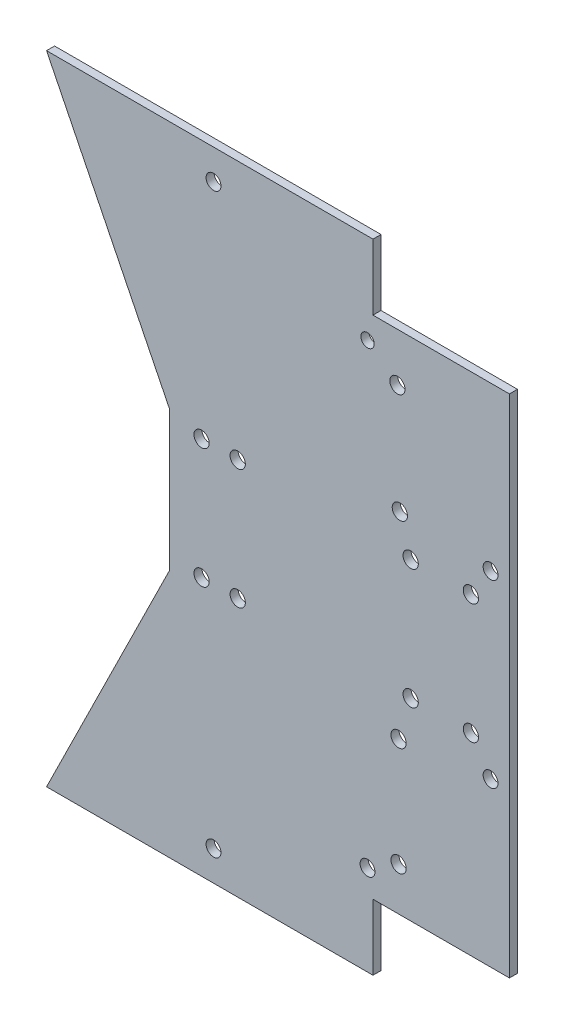
SolidWorks part; units mm, degrees
material "Thornel Mat VMA"
ref_plane "Front Plane" through (0, 0, 0) normal (0, 0, 1) x (1, 0, 0)
ref_plane "Top Plane" through (0, 0, 0) normal (0, 1, 0) x (1, 0, 0)
ref_plane "Right Plane" through (0, 0, 0) normal (1, 0, 0) x (0, 0, -1)
sketch "Sketch2" plane through (0, 0, 0) normal (0, 0, 1) x (-1, 0, 0)
  line L11 (-2.9301, 168.7083) -> (38.7094, 168.7083)
  line L12 (-2.9301, 8.6883) -> (38.7094, 8.6883)
  line L13 (38.7094, -12.1397) -> (38.7094, 8.6883)
  line L14 (143.4971, -12.1397) -> (38.7094, -12.1397)
  line L15 (38.7094, 189.5363) -> (38.7094, 168.7083)
  line L16 (143.4971, 189.5363) -> (38.7094, 189.5363)
  line L17 (104.6174, 110.8598) -> (143.4971, 189.5363)
  line L18 (104.6174, 66.5368) -> (143.4971, -12.1397)
  line L19 (104.6174, 66.5368) -> (72.8674, 66.5368)
  line L20 (72.8674, 66.5368) -> (72.8674, 110.8598)
  line L21 (104.6174, 110.8598) -> (72.8674, 110.8598)
  line L22 (-2.9301, 168.7083) -> (-2.9301, 8.6883)
  line L23 (41.9566, 19.6103) -> (41.9566, 13.2603) construction
  circle A0 centre (41.9566, 160.9613) radius 2.3495
  circle A1 centre (90.6739, 180.0113) radius 2.3495
  circle A2 centre (90.6739, -2.6147) radius 2.3495
  circle A3 centre (3.0351, 117.2098) radius 2.3495
  circle A4 centre (3.0351, 60.1868) radius 2.3495
  circle A5 centre (41.9566, 16.4353) radius 2.0955
  point P36 (41.9566, 16.4353)
  dimension "D3" = 4.699
  dimension "D7" = 31.75
  dimension "D8" = 41.6395
  dimension "D9" = 20.828
  dimension "D10" = 160.02
  dimension "D11" = 20.828
  dimension "D12" = 41.6395
  dimension "D13" = 104.7876
  dimension "D14" = 116.297
  dimension "D15" = 116.297
  dimension "D16" = 44.323
  dimension "D17" = 26.297
  dimension "D18" = 9.525
  dimension "D19" = 28.575
  dimension "D20" = 7.747
  dimension "D21" = 51.9645
  dimension "D22" = 51.4985
  dimension "D23" = 5.9651
  dimension "D24" = 51.4985
  dimension "D25" = 5.9651
  dimension "D26" = 7.747
  dimension "D27" = 3.2471
  dimension "D28" = 9.525
  dimension "D29" = 51.9645
extrude "Boss-Extrude1" add sketch "Sketch2" along normal blind 2.54
sketch "Sketch3" plane through (0, 0, 2.54) normal (0, 0, 1) x (1, 0, 0)
  line L1 (-104.6174, -66.5368) -> (-72.8674, -66.5368)
  line L2 (-104.6174, -66.5368) -> (-104.6174, -110.8598)
  line L3 (-104.6174, -110.8598) -> (-72.8674, -110.8598)
  line L4 (-72.8674, -66.5368) -> (-72.8674, -110.8598)
extrude "Boss-Extrude2" add sketch "Sketch3" against normal up to surface (2.54 mm away) up to face at (-65.9118, -88.6983, 0)
sketch "Sketch4" plane through (0, 0, 2.54) normal (0, 0, 1) x (1, 0, 0)
  line L0 (-104.6174, -66.5368) -> (-104.6174, -72.8868)
  line L1 (-104.6174, -66.5368) -> (-104.6174, -110.8598) construction
  line L2 (-104.6174, -69.7118) -> (2.9301, -69.7118) construction
  line L3 (2.9301, -168.7083) -> (2.9301, -8.6883) construction
  line L4 (-104.6174, -88.6983) -> (2.9301, -88.6983) construction
  line L5 (-104.6174, -107.6848) -> (2.9301, -107.6848) construction
  line L6 (-104.6174, -110.8598) -> (-104.6174, -104.5098)
  circle A0 centre (-94.4574, -69.7118) radius 2.413
  circle A1 centre (-83.0274, -69.7118) radius 2.413
  circle A2 centre (-28.3119, -69.7118) radius 2.413
  circle A3 centre (-9.2619, -69.7118) radius 2.413
  circle A4 centre (-9.2619, -107.6848) radius 2.413
  circle A5 centre (-28.3119, -107.6848) radius 2.413
  circle A6 centre (-83.0274, -107.6848) radius 2.413
  circle A7 centre (-94.4574, -107.6848) radius 2.413
  dimension "D2" = 10.16
  dimension "D4" = 4.826
  dimension "D5" = 4.826
  dimension "D8" = 4.826
  dimension "D9" = 4.826
  dimension "D1" = 3.175
  dimension "D3" = 11.43
  dimension "D6" = 19.05
  dimension "D7" = 12.192
extrude "Cut-Extrude1" cut sketch "Sketch4" against normal through all contours A0 | A1 | A2 | A3 | A4 | A5 | A6 | A7
sketch "Sketch5" plane through (0, 0, 2.54) normal (0, 0, 1) x (1, 0, 0)
  circle A0 centre (-31.739, -58.2731) radius 2.413
  dimension "D1" = 4.826
sketch "Sketch6" plane through (0, 0, 2.54) normal (0, 0, 1) x (1, 0, 0)
  circle A0 centre (-32.5114, -23.9918) radius 2.413
  dimension "D1" = 4.826
extrude "Cut-Extrude2" cut sketch "Sketch5" against normal through all
extrude "Cut-Extrude3" cut sketch "Sketch6" against normal through all
sketch "Sketch7" plane through (0, 0, 2.54) normal (0, 0, 1) x (1, 0, 0)
  circle A0 centre (-32.1405, -155.0714) radius 2.413
  circle A1 centre (-32.1405, -120.7814) radius 2.413
  dimension "D1" = 4.826
  dimension "D2" = 4.826
extrude "Cut-Extrude4" cut sketch "Sketch7" against normal through all
sketch "Sketch8" plane through (0, 0, 2.54) normal (0, 0, 1) x (1, 0, 0)
  line L0 (-38.7094, -168.7083) -> (2.9301, -168.7083) construction
  line L1 (-32.2387, 12.4252) -> (-40.2334, 12.4252)
  line L2 (-32.2387, 12.4252) -> (-32.2387, -8.6883)
  line L3 (-32.2387, -8.6883) -> (-40.2334, -8.6883)
  line L4 (-40.2334, 12.4252) -> (-40.2334, -8.6883)
  line L5 (-18.7398, -197.6692) -> (-40.2334, -197.6692)
  line L6 (-18.7398, -197.6692) -> (-18.7398, -168.7083)
  line L7 (-18.7398, -168.7083) -> (-40.2334, -168.7083)
  line L8 (-40.2334, -197.6692) -> (-40.2334, -168.7083)
  line L13 (-38.7094, -189.5363) -> (-38.7094, -168.7083) construction
  line L14 (2.9301, -8.6883) -> (-38.7094, -8.6883) construction
  point P8 (-44.1026, -170.287)
  dimension "D1" = 1.524
extrude "Cut-Extrude5" cut sketch "Sketch8" against normal through all
